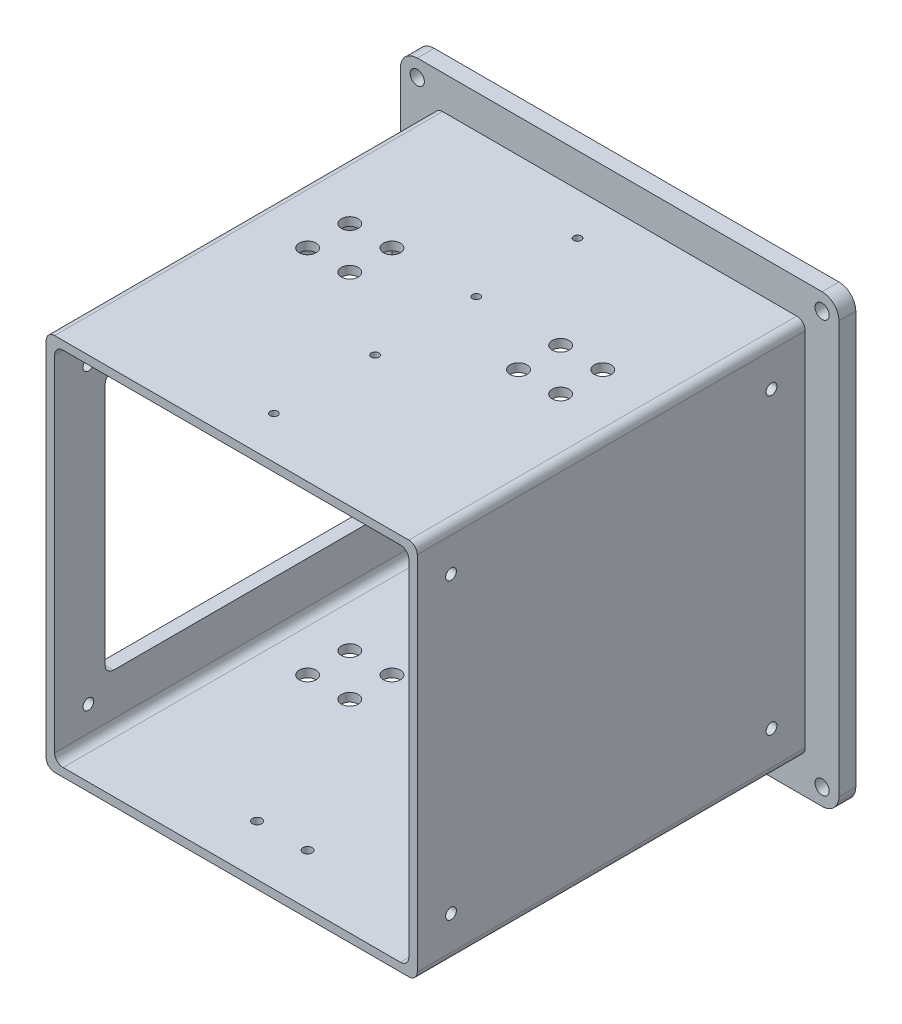
SolidWorks part; units mm, degrees
ref_plane "前视基准面" through (0, 0, 0) normal (0, 0, 1) x (1, 0, 0)
ref_plane "上视基准面" through (0, 0, 0) normal (0, 1, 0) x (1, 0, 0)
ref_plane "右视基准面" through (0, 0, 0) normal (1, 0, 0) x (0, 0, -1)
sketch "草图1" plane through (0, 0, 0) normal (0, 0, 1) x (1, 0, 0)
  line L1 (-105, -107.125) -> (105, -107.125)
  line L2 (-105, -107.125) -> (-105, 107.125)
  line L3 (-105, 107.125) -> (105, 107.125)
  line L4 (105, -107.125) -> (105, 107.125)
  line L5 (-105, -107.125) -> (105, 107.125) construction
  line L6 (-105, 107.125) -> (105, -107.125) construction
  line L7 (-110, -112.125) -> (110, -112.125)
  line L8 (-110, -112.125) -> (-110, 112.125)
  line L9 (-110, 112.125) -> (110, 112.125)
  line L10 (110, -112.125) -> (110, 112.125)
  line L11 (-110, -112.125) -> (110, 112.125) construction
  line L12 (-110, 112.125) -> (110, -112.125) construction
  point P0 (0, 0)
  point P6 (0, 0)
  dimension "D1" = 210
  dimension "D2" = 214.25
  dimension "D3" = 5
  dimension "D4" = 5
extrude "凸台-拉伸1" add sketch "草图1" along normal blind 230
sketch "草图2" plane through (0, 0, 0) normal (0, 0, -1) x (-1, 0, 0)
  line L0 (-110, 112.125) -> (110, 112.125) construction
  line L1 (-130, -132.125) -> (130, -132.125)
  line L2 (-130, -132.125) -> (-130, 132.125)
  line L3 (-130, 132.125) -> (130, 132.125)
  line L4 (130, -132.125) -> (130, 132.125)
  line L5 (-130, -132.125) -> (130, 132.125) construction
  line L6 (-130, 132.125) -> (130, -132.125) construction
  line L7 (-110, -112.125) -> (-110, 112.125) construction
  line L8 (105, 107.125) -> (105, -107.125) construction
  line L9 (105, -107.125) -> (-105, -107.125) construction
  line L10 (-105, -107.125) -> (-105, 107.125) construction
  line L11 (-105, 107.125) -> (105, 107.125) construction
  line L12 (105, 107.125) -> (105, -107.125)
  line L13 (105, -107.125) -> (-105, -107.125)
  line L14 (-105, -107.125) -> (-105, 107.125)
  line L15 (-105, 107.125) -> (105, 107.125)
  point P0 (0, 0)
  dimension "D1" = 20
  dimension "D2" = 20
extrude "凸台-拉伸2" add sketch "草图2" along normal blind 10
fillet "圆角1" radius 5 4 edges at (110, 112.125, 115) (110, -112.125, 115) (-110, -112.125, 115) (-110, 112.125, 115)
fillet "圆角2" radius 5 4 edges at (105, 107.125, 110) (-105, 107.125, 110) (105, -107.125, 110) (-105, -107.125, 110)
fillet "圆角3" radius 10 4 edges at (-130, 132.125, -5) (130, 132.125, -5) (130, -132.125, -5) (-130, -132.125, -5)
hole_wizard "Ø8.4 (8.4) 直径孔1" positions "草图3" profile "草图4" hole size "Ø8.4" standard "GB" end condition through all
sketch "草图3" plane through (0, 0, 0) normal (0, 0, 1) x (1, 0, 0)
  point P0 (120, 122.125)
  point P3 (120, -122.125)
  point P6 (-120, -122.125)
  point P10 (-120, 122.125)
sketch "草图4" plane through (120, 122.125, 0) normal (1, 0, 0) x (0, -1, 0)
  line L0 (0, 0) -> (0, 10)
  line L1 (0, 10) -> (4.2, 10)
  line L2 (4.2, 10) -> (4.2, 0)
  line L5 (4.2, 0) -> (0, 0)
  line L11 (0, -6.35) -> (0, 107.95) construction
  dimension "通孔孔直径" = 8.4
  dimension "通孔孔深度" = 10
sketch "草图18" plane through (0, 112.125, 0) normal (0, 1, 0) x (1, 0, 0)
  line L0 (105, -230) -> (-105, -230) construction
  line L1 (-105, 0) -> (-105, -230) construction
  line L2 (105, -230) -> (105, 0) construction
  point P0 (-75, -85)
  point P1 (-75, -110)
  point P2 (-50, -110)
  point P3 (-50, -85)
  point P5 (50, -110)
  point P6 (75, -110)
  point P8 (75, -85)
  point P16 (50, -85)
  dimension "D1" = 25
  dimension "D2" = 25
  dimension "D3" = 35.3553
  dimension "D4" = 25
  dimension "D5" = 35.3553
  dimension "D6" = 25
  dimension "D7" = 30
  dimension "D8" = 30
  dimension "D9" = 25
  dimension "D10" = 25
  dimension "D11" = 25
  dimension "D12" = 25
  dimension "D13" = 120
  dimension "D14" = 120
  dimension "D15" = 35.3553
  dimension "D16" = 55
hole_wizard "大小mm 暗销孔11" positions "草图33" profile "草图34" hole size "Ø10.0" standard "GB" end condition through all
sketch "草图33" plane through (0, 112.125, 0) normal (0, 1, 0) x (1, 0, 0)
  point P0 (-75, -85)
  point P3 (-50, -85)
  point P6 (-50, -110)
  point P9 (-75, -110)
  point P12 (50, -110)
  point P15 (50, -85)
  point P18 (75, -85)
  point P21 (75, -110)
sketch "草图34" plane through (-75, 112.125, 85) normal (1, 0, 0) x (0, 0, 1)
  line L0 (0, 0) -> (0, 244.25)
  line L1 (0, 244.25) -> (5, 244.25)
  line L2 (5, 244.25) -> (5, 0)
  line L5 (5, 0) -> (0, 0)
  line L11 (0, -6.35) -> (0, 107.95) construction
  dimension "通孔孔直径" = 10
  dimension "通孔孔深度" = 244.25
sketch "草图35" plane through (0, -112.125, 0) normal (0, -1, 0) x (1, 0, 0)
  line L0 (120, 0) -> (-120, 0) construction
  line L2 (-105, 0) -> (105, 0) construction
  line L3 (105, 0) -> (105, 230) construction
  line L4 (-105, 230) -> (-105, 0) construction
  point P0 (15, 200)
  point P1 (19, 25.5)
  point P2 (-19, 25.5)
  point P4 (-15, 200)
  dimension "D1" = 90
  dimension "D2" = 38
  dimension "D4" = 19
  dimension "D5" = 200
  dimension "D6" = 200
  dimension "D7" = 25.5
  dimension "D8" = 25.5
  dimension "D9" = 90
sketch "草图38" plane through (0, 112.125, 0) normal (0, 1, 0) x (1, 0, 0)
  line L0 (-105, 0) -> (-105, -230) construction
  line L2 (105, 0) -> (-105, 0) construction
  point P0 (0, -25)
  point P1 (0, -85)
  point P2 (0, -205)
  point P3 (0, -145)
  dimension "D1" = 105
  dimension "D2" = 60
  dimension "D3" = 60
  dimension "D4" = 60
  dimension "D5" = 25
  dimension "D6" = 105
  dimension "D7" = 105
  dimension "D8" = 105
hole_wizard "Ø4.5 (4.5) 直径孔1" positions "草图39" profile "草图40" hole size "Ø4.5" standard "GB" end condition up to next
sketch "草图39" plane through (0, 112.125, 0) normal (0, 1, 0) x (1, 0, 0)
  point P0 (0, -25)
  point P3 (0, -85)
  point P6 (0, -145)
  point P9 (0, -205)
sketch "草图40" plane through (0, 112.125, 25) normal (1, 0, 0) x (0, 0, 1)
  line L0 (0, 0) -> (0, 5)
  line L1 (0, 5) -> (2.25, 5)
  line L2 (2.25, 5) -> (2.25, 0)
  line L5 (2.25, 0) -> (0, 0)
  line L11 (0, -6.35) -> (0, 107.95) construction
  dimension "通孔孔直径" = 4.5
  dimension "通孔孔深度" = 5
hole_wizard "Ø6.6 (6.6) 直径孔1" positions "草图41" profile "草图42" hole size "Ø6.6" standard "GB" end condition up to next
sketch "草图41" plane through (0, -112.125, 0) normal (0, -1, 0) x (-1, 0, 0)
  point P0 (19, -25.5)
  point P3 (-19, -25.5)
sketch "草图42" plane through (-19, -112.125, 25.5) normal (1, 0, 0) x (0, 0, -1)
  line L0 (0, 0) -> (0, 5)
  line L1 (0, 5) -> (3.3, 5)
  line L2 (3.3, 5) -> (3.3, 0)
  line L5 (3.3, 0) -> (0, 0)
  line L11 (0, -6.35) -> (0, 107.95) construction
  dimension "通孔孔直径" = 6.6
  dimension "通孔孔深度" = 5
hole_wizard "Ø5.5 (5.5) 直径孔1" positions "草图43" profile "草图44" hole size "Ø5.5" standard "GB" end condition up to next
sketch "草图43" plane through (0, -112.125, 0) normal (0, -1, 0) x (-1, 0, 0)
  point P0 (15, -200)
  point P3 (-15, -200)
sketch "草图44" plane through (-15, -112.125, 200) normal (1, 0, 0) x (0, 0, -1)
  line L0 (0, 0) -> (0, 5)
  line L1 (0, 5) -> (2.75, 5)
  line L2 (2.75, 5) -> (2.75, 0)
  line L5 (2.75, 0) -> (0, 0)
  line L11 (0, -6.35) -> (0, 107.95) construction
  dimension "通孔孔直径" = 5.5
  dimension "通孔孔深度" = 5
sketch "草图45" plane through (-110, 0, 0) normal (-1, 0, 0) x (0, 0, 1)
  line L0 (230, 107.125) -> (0, 107.125) construction
  line L1 (200, -77.125) -> (30, -77.125)
  line L2 (200, -77.125) -> (200, 77.125)
  line L3 (200, 77.125) -> (30, 77.125)
  line L4 (30, -77.125) -> (30, 77.125)
  line L5 (200, -77.125) -> (30, 77.125) construction
  line L6 (200, 77.125) -> (30, -77.125) construction
  line L7 (0, -107.125) -> (230, -107.125) construction
  line L8 (0, -122.125) -> (0, 122.125) construction
  line L9 (230, 107.125) -> (230, -107.125) construction
  point P0 (115, 0)
  dimension "D1" = 30
  dimension "D2" = 30
  dimension "D3" = 30
  dimension "D4" = 30
extrude "切除-拉伸1" cut sketch "草图45" against normal up to next
fillet "圆角4" radius 5 4 edges at (-107.5, -77.125, 30) (-107.5, -77.125, 200) (-107.5, 77.125, 200) (-107.5, 77.125, 30)
sketch "草图46" plane through (110, 0, 0) normal (1, 0, 0) x (0, 0, -1)
  line L0 (-195, 77.125) -> (-35, 77.125) construction
  line L1 (-200, -72.125) -> (-200, 72.125) construction
  line L2 (-30, 72.125) -> (-30, -72.125) construction
  line L3 (-35, -77.125) -> (-195, -77.125) construction
  point P0 (-210, 87.125)
  point P1 (-210, -87.125)
  point P2 (-20, -87.125)
  point P3 (-20, 87.125)
  dimension "D1" = 10
  dimension "D2" = 10
  dimension "D3" = 10
  dimension "D4" = 10
  dimension "D5" = 10
  dimension "D6" = 10
  dimension "D7" = 10
  dimension "D8" = 10
hole_wizard "Ø6.4 (6.4) 直径孔1" positions "草图47" profile "草图48" hole size "Ø6.4" standard "GB" end condition through all
sketch "草图47" plane through (110, 0, 0) normal (1, 0, 0) x (0, 0, -1)
  point P0 (-210, 87.125)
  point P3 (-20, 87.125)
  point P6 (-20, -87.125)
  point P9 (-210, -87.125)
sketch "草图48" plane through (110, 87.125, 210) normal (0, 1, 0) x (0, 0, -1)
  line L0 (0, 0) -> (0, 240)
  line L1 (0, 240) -> (3.2, 240)
  line L2 (3.2, 240) -> (3.2, 0)
  line L5 (3.2, 0) -> (0, 0)
  line L11 (0, -6.35) -> (0, 107.95) construction
  dimension "通孔孔直径" = 6.4
  dimension "通孔孔深度" = 240
sketch "草图49" plane through (-110, 0, 0) normal (-1, 0, 0) x (0, 0, 1)
  line L0 (195, 77.125) -> (35, 77.125) construction
  line L1 (27, 80.125) -> (203, 80.125)
  line L2 (27, 80.125) -> (27, -80.125)
  line L3 (27, -80.125) -> (203, -80.125)
  line L4 (203, 80.125) -> (203, -80.125)
  line L5 (35, -77.125) -> (195, -77.125) construction
  line L6 (30, 72.125) -> (30, -72.125) construction
  line L7 (200, -72.125) -> (200, 72.125) construction
  line L8 (200, -72.125) -> (200, 72.125)
  line L9 (35, -77.125) -> (195, -77.125)
  line L10 (30, 72.125) -> (30, -72.125)
  line L11 (195, 77.125) -> (35, 77.125)
  arc A0 (200, 72.125) -> (195, 77.125) centre (195, 72.125) ccw construction
  arc A1 (195, -77.125) -> (200, -72.125) centre (195, -72.125) ccw construction
  arc A2 (30, -72.125) -> (35, -77.125) centre (35, -72.125) ccw construction
  arc A3 (35, 77.125) -> (30, 72.125) centre (35, 72.125) ccw construction
  arc A4 (200, 72.125) -> (195, 77.125) centre (195, 72.125) ccw
  arc A5 (195, -77.125) -> (200, -72.125) centre (195, -72.125) ccw
  arc A6 (30, -72.125) -> (35, -77.125) centre (35, -72.125) ccw
  arc A7 (35, 77.125) -> (30, 72.125) centre (35, 72.125) ccw
  dimension "D1" = 3
  dimension "D2" = 3
  dimension "D3" = 3
  dimension "D4" = 3
extrude "凸台-拉伸3" add sketch "草图49" along normal blind 3
fillet "圆角5" radius 5 4 edges at (-111.5, 80.125, 27) (-111.5, -80.125, 27) (-111.5, -80.125, 203) (-111.5, 80.125, 203)
sketch "草图50" plane through (0, 0, -10) normal (0, 0, -1) x (-1, 0, 0)
  line L0 (100, 107.125) -> (-100, 107.125) construction
  line L1 (108, -110.125) -> (-108, -110.125)
  line L2 (108, -110.125) -> (108, 110.125)
  line L3 (108, 110.125) -> (-108, 110.125)
  line L4 (-108, -110.125) -> (-108, 110.125)
  line L5 (108, -110.125) -> (-108, 110.125) construction
  line L6 (108, 110.125) -> (-108, -110.125) construction
  line L7 (-105, 102.125) -> (-105, -102.125) construction
  line L8 (-100, -107.125) -> (100, -107.125) construction
  line L9 (105, -102.125) -> (105, 102.125) construction
  line L10 (-100, -107.125) -> (100, -107.125)
  line L11 (105, -102.125) -> (105, 102.125)
  line L12 (100, 107.125) -> (-100, 107.125)
  line L13 (-105, 102.125) -> (-105, -102.125)
  arc A0 (-105, -102.125) -> (-100, -107.125) centre (-100, -102.125) ccw construction
  arc A1 (100, -107.125) -> (105, -102.125) centre (100, -102.125) ccw construction
  arc A2 (105, 102.125) -> (100, 107.125) centre (100, 102.125) ccw construction
  arc A3 (-100, 107.125) -> (-105, 102.125) centre (-100, 102.125) ccw construction
  arc A4 (-105, -102.125) -> (-100, -107.125) centre (-100, -102.125) ccw
  arc A5 (100, -107.125) -> (105, -102.125) centre (100, -102.125) ccw
  arc A6 (105, 102.125) -> (100, 107.125) centre (100, 102.125) ccw
  arc A7 (-100, 107.125) -> (-105, 102.125) centre (-100, 102.125) ccw
  point P0 (0, 0)
  dimension "D1" = 3
  dimension "D2" = 3
extrude "凸台-拉伸4" add sketch "草图50" along normal blind 3
fillet "圆角6" radius 5 4 edges at (-108, 110.125, -11.5) (-108, -110.125, -11.5) (108, -110.125, -11.5) (108, 110.125, -11.5)
